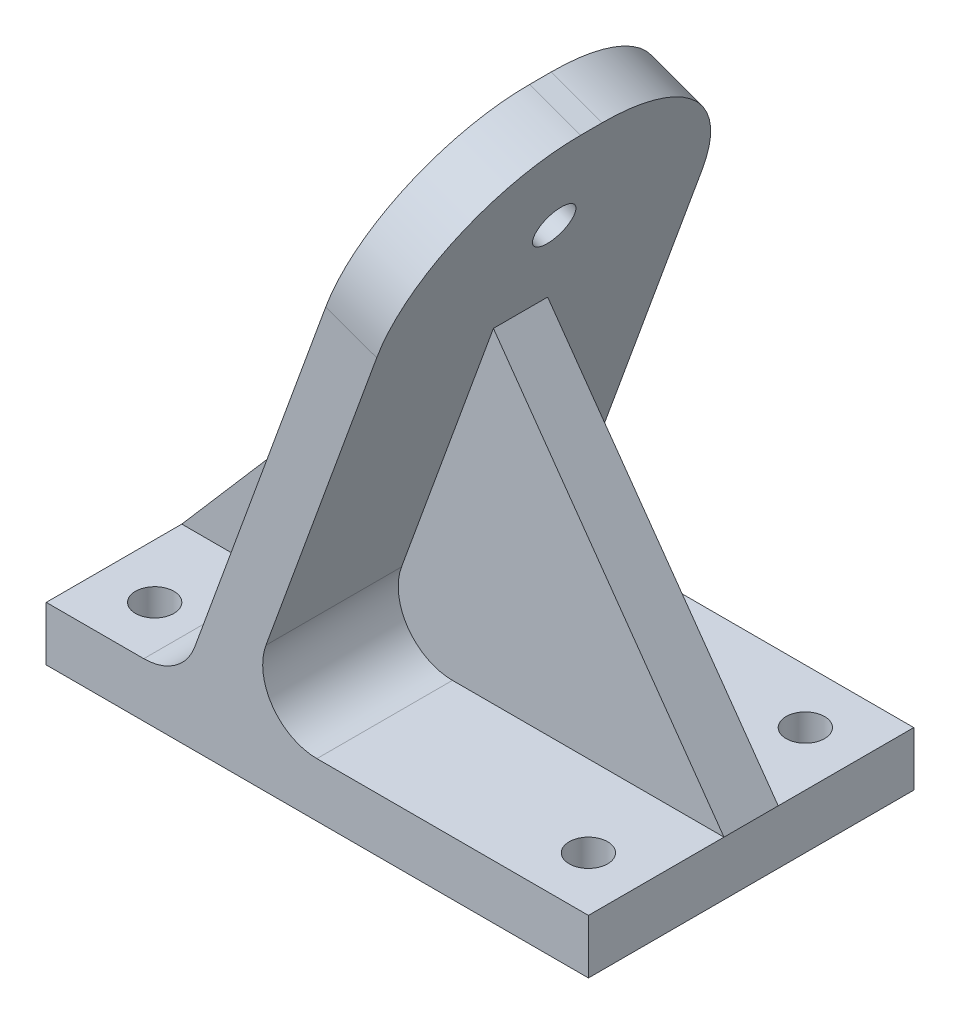
SolidWorks part; units mm, degrees
material "PLA Black"
ref_plane "Front Plane" through (0, 0, 0) normal (0, 0, 1) x (1, 0, 0)
ref_plane "Top Plane" through (0, 0, 0) normal (0, 1, 0) x (1, 0, 0)
ref_plane "Right Plane" through (0, 0, 0) normal (1, 0, 0) x (0, 0, -1)
sketch "Sketch1" plane through (0, 0, 0) normal (0, 1, 0) x (1, 0, 0)
  line L1 (-31.75, -19.05) -> (31.75, -19.05)
  line L2 (-31.75, -19.05) -> (-31.75, 19.05)
  line L3 (-31.75, 19.05) -> (31.75, 19.05)
  line L4 (31.75, -19.05) -> (31.75, 19.05)
  line L5 (-31.75, -19.05) -> (31.75, 19.05) construction
  line L6 (-31.75, 19.05) -> (31.75, -19.05) construction
  point P0 (0, 0)
  dimension "D1" = 63.5
  dimension "D2" = 38.1
extrude "Boss-Extrude1" add sketch "Sketch1" along normal blind 6.35
sketch "Sketch2" plane through (0, 0, 19.05) normal (0, 0, 1) x (1, 0, 0)
  line L0 (-11.43, 0) -> (13.0366, 67.2214)
  line L1 (-11.43, 0) -> (-17.397, 2.1718)
  line L2 (13.0366, 67.2214) -> (7.0695, 69.3932)
  line L3 (-17.397, 2.1718) -> (7.0695, 69.3932)
  line L4 (-11.43, 0) -> (7.0695, 69.3932) construction
  line L5 (13.0366, 67.2214) -> (-17.397, 2.1718) construction
  line L6 (31.75, 6.35) -> (31.75, 0) construction
  line L7 (-31.75, 0) -> (31.75, 0) construction
  point P1 (-2.1802, 34.6966)
  dimension "D1" = 20
  dimension "D2" = 50.8
  dimension "D3" = 11.43
extrude "Boss-Extrude2" add sketch "Sketch2" against normal up to surface (38.1 mm away) up to face at (0, 3.175, -19.05)
fillet "Fillet1" radius 17.78 2 edges at (10.0531, 68.3073, 19.05) (10.0531, 68.3073, -19.05)
sketch "Sketch4" plane through (0, 6.35, 0) normal (0, 1, 0) x (1, 0, 0)
  circle A0 centre (25.4, -12.7) radius 2.25 construction
  circle A1 centre (-25.4, -12.7) radius 2.25 construction
  circle A2 centre (25.4, 12.7) radius 2.25 construction
  circle A3 centre (-25.4, 12.7) radius 2.25 construction
  circle A4 centre (25.4, -12.7) radius 2.25
  circle A5 centre (-25.4, -12.7) radius 2.25
  circle A6 centre (25.4, 12.7) radius 2.25
  circle A7 centre (-25.4, 12.7) radius 2.25
extrude "Cut-Extrude2" cut sketch "Sketch4" against normal through all
sketch "Sketch5" plane through (-16.06, 5.8454, 0) normal (-0.9397, 0.342, 0) x (0, 0, 1)
  line L0 (-1.27, 67.6262) -> (1.27, 67.6262) construction
  circle A0 centre (0, 54.9262) radius 2.413
  point P6 (0, 67.6262)
  dimension "D1" = 4.826
  dimension "D2" = 12.7
fillet "Fillet2" radius 6.35 2 edges at (-15.8763, 6.35, 0) (-9.1188, 6.35, 0)
sketch "Sketch7" plane through (0, 0, 0) normal (0, 0, 1) x (1, 0, 0)
  line L0 (4.7485, 44.45) -> (31.75, 6.35)
  line L1 (-0.05, 6.35) -> (31.75, 6.35) construction
  line L4 (-0.05, 6.35) -> (31.75, 6.35)
  line L7 (-31.75, 6.35) -> (-4.3203, 38.1)
  line L8 (0.9884, 52.6855) -> (-14.3556, 10.5282) construction
  line L9 (-31.75, 6.35) -> (-20.3226, 6.35) construction
  line L10 (-4.3203, 38.1) -> (-14.3556, 10.5282)
  line L11 (-31.75, 6.35) -> (-20.3226, 6.35)
  line L13 (-6.0171, 14.8718) -> (4.7485, 44.45)
  line L14 (-6.0171, 14.8718) -> (6.9555, 50.5136) construction
  arc A0 (-6.0171, 14.8718) -> (-0.05, 6.35) centre (-0.05, 12.7) ccw construction
  arc A1 (-6.0171, 14.8718) -> (-0.05, 6.35) centre (-0.05, 12.7) ccw
  arc A2 (-20.3226, 6.35) -> (-14.3556, 10.5282) centre (-20.3226, 12.7) ccw construction
  arc A3 (-20.3226, 6.35) -> (-14.3556, 10.5282) centre (-20.3226, 12.7) ccw
  dimension "D1" = 31.75
  dimension "D2" = 38.1
extrude "Boss-Extrude5" add sketch "Sketch7" along normal mid plane 6.35
extrude "Cut-Extrude3" cut sketch "Sketch5" against normal through all
